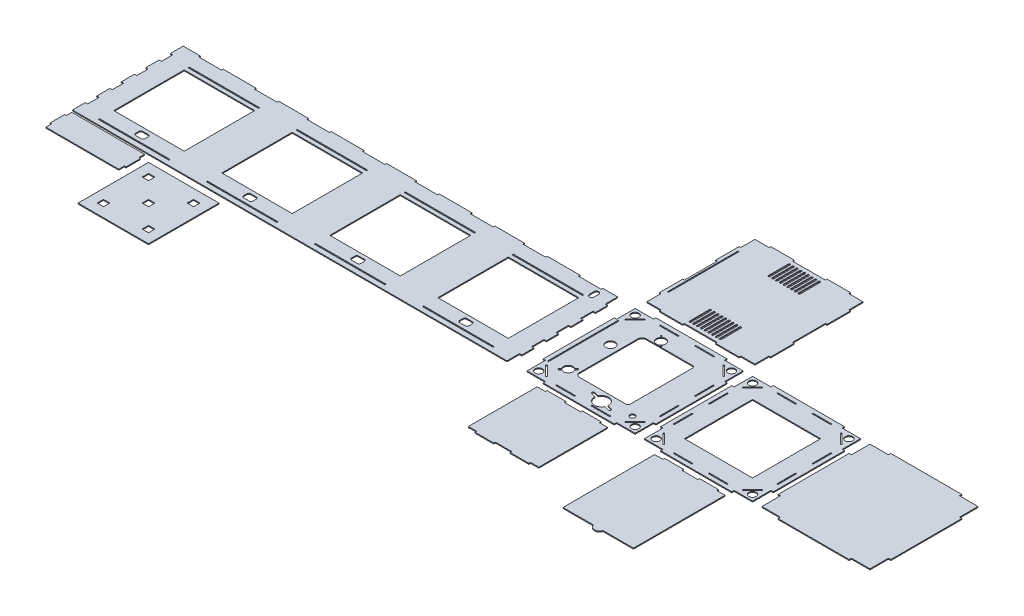
SolidWorks part; units mm, degrees
ref_plane "Front" through (0, 0, 0) normal (0, 0, 1) x (1, 0, 0)
ref_plane "Top" through (0, 0, 0) normal (0, 1, 0) x (1, 0, 0)
ref_plane "Right" through (0, 0, 0) normal (1, 0, 0) x (0, 0, -1)
sketch "Sketch1" plane through (0, 0, 0) normal (0, 1, 0) x (1, 0, 0)
  line L0 (0, 0) -> (438.15, 0) construction
  line L2 (-146.05, 149.606) -> (-146.05, -149.606) construction
  line L4 (146.05, 149.606) -> (146.05, -149.606) construction
  line L5 (-146.05, 149.606) -> (146.05, -149.606) construction
  line L6 (-146.05, -149.606) -> (146.05, 149.606) construction
  line L11 (146.05, 149.606) -> (438.15, 149.606)
  line L12 (146.05, 149.606) -> (146.05, -149.606) construction
  line L13 (146.05, -149.606) -> (438.15, -149.606)
  line L14 (438.15, 149.606) -> (438.15, -149.606) construction
  line L19 (-146.05, -149.606) -> (-438.15, -149.606)
  line L20 (-146.05, -149.606) -> (-146.05, 149.606) construction
  line L21 (-146.05, 149.606) -> (-438.15, 149.606)
  line L28 (146.05, -149.606) -> (-146.05, -149.606)
  line L34 (146.05, 149.606) -> (-146.05, 149.606)
  line L35 (-438.15, 149.606) -> (-438.15, -149.606) construction
  line L43 (-438.15, 149.606) -> (-730.25, 149.606)
  line L44 (-730.25, 149.606) -> (-730.25, -149.606) construction
  line L45 (-730.25, -149.606) -> (-438.15, -149.606)
  line L46 (438.15, 149.606) -> (438.15, 116.078)
  line L47 (438.15, 116.078) -> (444.5, 116.078)
  line L48 (444.5, 116.078) -> (444.5, 83.185)
  line L49 (444.5, 83.185) -> (438.15, 83.185)
  line L50 (438.15, 83.185) -> (438.15, 49.657)
  line L51 (438.15, 49.657) -> (444.5, 49.657)
  line L63 (444.5, 49.657) -> (444.5, 16.764)
  line L64 (444.5, 16.764) -> (438.15, 16.764)
  line L65 (438.15, 16.764) -> (438.15, -16.764)
  line L66 (438.15, -16.764) -> (444.5, -16.764)
  line L67 (444.5, -16.764) -> (444.5, -49.657)
  line L68 (444.5, -49.657) -> (438.15, -49.657)
  line L69 (438.15, -49.657) -> (438.15, -83.185)
  line L70 (438.15, -83.185) -> (444.5, -83.185)
  line L71 (444.5, -83.185) -> (444.5, -116.078)
  line L72 (444.5, -116.078) -> (438.15, -116.078)
  line L73 (438.15, -116.078) -> (438.15, -149.606)
  line L74 (-730.25, 149.606) -> (-736.6, 149.606)
  line L76 (-736.6, 114.8715) -> (-730.25, 114.8715)
  line L78 (-730.25, 84.3915) -> (-736.6, 84.3915)
  line L80 (-736.6, 48.4505) -> (-730.25, 48.4505)
  line L82 (-730.25, 17.9705) -> (-736.6, 17.9705)
  line L84 (-736.6, -17.9705) -> (-730.25, -17.9705)
  line L86 (-730.25, -48.4505) -> (-736.6, -48.4505)
  line L88 (-736.6, -84.3915) -> (-730.25, -84.3915)
  line L90 (-730.25, -114.8715) -> (-736.6, -114.8715)
  line L92 (-736.6, -149.606) -> (-730.25, -149.606)
  line L93 (444.5, 33.2105) -> (-730.25, 33.2105) construction
  line L94 (-730.25, 99.6315) -> (444.5, 99.6315) construction
  line L95 (-736.6, 149.606) -> (-736.6, 114.8715)
  line L96 (-736.6, 84.3915) -> (-736.6, 48.4505)
  line L97 (-730.25, 114.8715) -> (-730.25, 84.3915)
  line L98 (-730.25, 48.4505) -> (-730.25, 17.9705)
  line L99 (-730.25, -17.9705) -> (-730.25, -48.4505)
  line L100 (-730.25, -84.3915) -> (-730.25, -114.8715)
  line L101 (-730.25, -99.6315) -> (444.5, -99.6315) construction
  line L102 (-730.25, -33.2105) -> (444.5, -33.2105) construction
  line L103 (-736.6, 17.9705) -> (-736.6, -17.9705)
  line L104 (-736.6, -48.4505) -> (-736.6, -84.3915)
  line L105 (-736.6, -114.8715) -> (-736.6, -149.606)
  point P0 (0, 0)
  dimension "D1" = 292.1
  dimension "D2" = 299.212
  dimension "D3" = 6.35
  dimension "D4" = 32.893
  dimension "D5" = 30.48
extrude "Boss-Extrude1" add sketch "Sketch1" along normal blind 2.54
sketch "Sketch4" plane through (0, 2.54, 0) normal (0, 1, 0) x (1, 0, 0)
  line L0 (-438.15, 149.606) -> (-438.15, -149.606) construction
  line L1 (-438.15, 149.606) -> (-438.15, -149.606)
  line L2 (-146.05, 149.606) -> (-146.05, -149.606) construction
  line L3 (-146.05, 149.606) -> (-146.05, -149.606)
  line L4 (146.05, 149.606) -> (146.05, -149.606) construction
  line L5 (146.05, 149.606) -> (146.05, -149.606)
sketch "Sketch5" plane through (0, 2.54, 0) normal (0, 1, 0) x (1, 0, 0)
  line L0 (-730.25, -17.9705) -> (-730.25, 17.9705) construction
  line L1 (-438.15, 0) -> (-730.25, 0) construction
  line L2 (-438.15, 149.606) -> (-438.15, -149.606) construction
  line L3 (-438.15, 0) -> (-146.05, 0) construction
  line L4 (-146.05, 149.606) -> (-146.05, -149.606) construction
  line L5 (-146.05, 0) -> (146.05, 0) construction
  line L6 (146.05, 149.606) -> (146.05, -149.606) construction
  line L7 (146.05, 0) -> (438.15, 0) construction
  line L8 (438.15, -16.764) -> (438.15, 16.764) construction
  line L9 (-584.2, 0) -> (-584.2, -149.606) construction
  line L10 (-736.6, -149.606) -> (438.15, -149.606) construction
  line L11 (-292.1, 0) -> (-292.1, -149.606) construction
  line L12 (0, 0) -> (0, -149.606) construction
  line L13 (292.1, 0) -> (292.1, -149.606) construction
  line L14 (-488.95, -136.906) -> (-488.95, -149.606) construction
  line L15 (-679.45, -133.604) -> (-488.95, -133.604)
  line L16 (-679.45, -133.604) -> (-679.45, -136.906)
  line L17 (-679.45, -136.906) -> (-488.95, -136.906)
  line L18 (-488.95, -133.604) -> (-488.95, -136.906)
  line L19 (-679.45, -133.604) -> (-488.95, -136.906) construction
  line L20 (-679.45, -136.906) -> (-488.95, -133.604) construction
  line L21 (-387.35, -133.604) -> (-196.85, -133.604)
  line L22 (-387.35, -133.604) -> (-387.35, -136.906)
  line L23 (-387.35, -136.906) -> (-196.85, -136.906)
  line L24 (-196.85, -133.604) -> (-196.85, -136.906)
  line L25 (-387.35, -133.604) -> (-196.85, -136.906) construction
  line L26 (-387.35, -136.906) -> (-196.85, -133.604) construction
  line L27 (-95.25, -136.906) -> (95.25, -136.906)
  line L28 (-95.25, -136.906) -> (-95.25, -133.604)
  line L29 (-95.25, -133.604) -> (95.25, -133.604)
  line L30 (95.25, -136.906) -> (95.25, -133.604)
  line L31 (-95.25, -136.906) -> (95.25, -133.604) construction
  line L32 (-95.25, -133.604) -> (95.25, -136.906) construction
  line L33 (196.85, -136.906) -> (387.35, -136.906)
  line L34 (196.85, -136.906) -> (196.85, -133.604)
  line L35 (196.85, -133.604) -> (387.35, -133.604)
  line L36 (387.35, -136.906) -> (387.35, -133.604)
  line L37 (196.85, -136.906) -> (387.35, -133.604) construction
  line L38 (196.85, -133.604) -> (387.35, -136.906) construction
  line L39 (196.85, 133.604) -> (387.35, 136.906) construction
  line L40 (196.85, 136.906) -> (387.35, 133.604) construction
  line L41 (-95.25, 133.604) -> (95.25, 136.906) construction
  line L42 (-95.25, 136.906) -> (95.25, 133.604) construction
  line L43 (-387.35, 136.906) -> (-196.85, 133.604) construction
  line L44 (-387.35, 133.604) -> (-196.85, 136.906) construction
  line L45 (-679.45, 136.906) -> (-488.95, 133.604) construction
  line L46 (-679.45, 133.604) -> (-488.95, 136.906) construction
  line L47 (-584.2, 0) -> (-584.2, 107.061) construction
  line L48 (387.35, 136.906) -> (387.35, 133.604) construction
  line L49 (196.85, 133.604) -> (387.35, 133.604) construction
  line L50 (196.85, 136.906) -> (196.85, 133.604) construction
  line L51 (196.85, 136.906) -> (387.35, 136.906) construction
  line L52 (95.25, 136.906) -> (95.25, 133.604) construction
  line L53 (-95.25, 133.604) -> (95.25, 133.604) construction
  line L54 (-95.25, 136.906) -> (-95.25, 133.604) construction
  line L55 (-95.25, 136.906) -> (95.25, 136.906) construction
  line L56 (-196.85, 133.604) -> (-196.85, 136.906) construction
  line L57 (-387.35, 136.906) -> (-196.85, 136.906) construction
  line L58 (-387.35, 133.604) -> (-387.35, 136.906) construction
  line L59 (-387.35, 133.604) -> (-196.85, 133.604) construction
  line L60 (-488.95, 133.604) -> (-488.95, 136.906) construction
  line L61 (-679.45, 136.906) -> (-488.95, 136.906) construction
  line L62 (-679.45, 133.604) -> (-679.45, 136.906) construction
  line L63 (-679.45, 133.604) -> (-488.95, 133.604) construction
  line L64 (-292.1, 0) -> (-292.1, 107.061) construction
  line L65 (-679.45, 95.25) -> (-488.95, 95.25)
  line L66 (-679.45, 95.25) -> (-679.45, -95.25)
  line L67 (-679.45, -95.25) -> (-488.95, -95.25)
  line L68 (-488.95, 95.25) -> (-488.95, -95.25)
  line L69 (-679.45, 95.25) -> (-488.95, -95.25) construction
  line L70 (-679.45, -95.25) -> (-488.95, 95.25) construction
  line L71 (-387.35, 95.25) -> (-196.85, 95.25)
  line L72 (-387.35, 95.25) -> (-387.35, -95.25)
  line L73 (-387.35, -95.25) -> (-196.85, -95.25)
  line L74 (-196.85, 95.25) -> (-196.85, -95.25)
  line L75 (-387.35, 95.25) -> (-196.85, -95.25) construction
  line L76 (-387.35, -95.25) -> (-196.85, 95.25) construction
  line L77 (-95.25, 95.25) -> (95.25, 95.25)
  line L78 (-95.25, 95.25) -> (-95.25, -95.25)
  line L79 (-95.25, -95.25) -> (95.25, -95.25)
  line L80 (95.25, 95.25) -> (95.25, -95.25)
  line L81 (-95.25, 95.25) -> (95.25, -95.25) construction
  line L82 (-95.25, -95.25) -> (95.25, 95.25) construction
  line L83 (196.85, 95.25) -> (387.35, 95.25)
  line L84 (196.85, 95.25) -> (196.85, -95.25)
  line L85 (196.85, -95.25) -> (387.35, -95.25)
  line L86 (387.35, 95.25) -> (387.35, -95.25)
  line L87 (196.85, 95.25) -> (387.35, -95.25) construction
  line L88 (196.85, -95.25) -> (387.35, 95.25) construction
  line L89 (0, 0) -> (0, 107.061) construction
  line L90 (292.1, 0) -> (292.1, 107.061) construction
  line L91 (-387.35, -95.25) -> (-387.35, -133.604) construction
  line L92 (-679.45, 108.712) -> (-488.95, 108.712)
  line L93 (-679.45, 108.712) -> (-679.45, 105.41)
  line L94 (-679.45, 105.41) -> (-488.95, 105.41)
  line L95 (-488.95, 108.712) -> (-488.95, 105.41)
  line L96 (-679.45, 108.712) -> (-488.95, 105.41) construction
  line L97 (-679.45, 105.41) -> (-488.95, 108.712) construction
  line L98 (-387.35, 108.712) -> (-196.85, 108.712)
  line L99 (-387.35, 108.712) -> (-387.35, 105.41)
  line L100 (-387.35, 105.41) -> (-196.85, 105.41)
  line L101 (-196.85, 108.712) -> (-196.85, 105.41)
  line L102 (-387.35, 108.712) -> (-196.85, 105.41) construction
  line L103 (-387.35, 105.41) -> (-196.85, 108.712) construction
  line L104 (-95.25, 108.712) -> (95.25, 108.712)
  line L105 (-95.25, 108.712) -> (-95.25, 105.41)
  line L106 (-95.25, 105.41) -> (95.25, 105.41)
  line L107 (95.25, 108.712) -> (95.25, 105.41)
  line L108 (-95.25, 108.712) -> (95.25, 105.41) construction
  line L109 (-95.25, 105.41) -> (95.25, 108.712) construction
  line L110 (196.85, 108.712) -> (387.35, 108.712)
  line L111 (196.85, 108.712) -> (196.85, 105.41)
  line L112 (196.85, 105.41) -> (387.35, 105.41)
  line L113 (387.35, 108.712) -> (387.35, 105.41)
  line L114 (196.85, 108.712) -> (387.35, 105.41) construction
  line L115 (196.85, 105.41) -> (387.35, 108.712) construction
  line L116 (-196.85, -95.25) -> (-196.85, -133.604) construction
  line L117 (-196.85, -114.427) -> (-387.35, -114.427) construction
  line L118 (-7.62, -124.079) -> (7.62, -124.079)
  line L119 (-299.72, -104.775) -> (-284.48, -104.775)
  line L120 (-304.8, -109.855) -> (-304.8, -118.999)
  line L121 (-299.72, -124.079) -> (-284.48, -124.079)
  line L122 (-279.4, -109.855) -> (-279.4, -118.999)
  line L123 (-304.8, -104.775) -> (-279.4, -124.079) construction
  line L124 (-304.8, -124.079) -> (-279.4, -104.775) construction
  line L125 (-12.7, -109.855) -> (-12.7, -118.999)
  line L126 (-7.62, -104.775) -> (7.62, -104.775)
  line L127 (12.7, -109.855) -> (12.7, -118.999)
  line L128 (284.48, -124.079) -> (299.72, -124.079)
  line L129 (279.4, -109.855) -> (279.4, -118.999)
  line L130 (284.48, -104.775) -> (299.72, -104.775)
  line L131 (304.8, -109.855) -> (304.8, -118.999)
  line L132 (-596.9, -109.855) -> (-596.9, -118.999)
  line L133 (-591.82, -104.775) -> (-576.58, -104.775)
  line L134 (-571.5, -109.855) -> (-571.5, -118.999)
  line L135 (-591.82, -124.079) -> (-576.58, -124.079)
  line L136 (438.15, 149.606) -> (-736.6, 149.606) construction
  line L137 (400.05, 130.302) -> (400.05, 117.602) construction
  line L138 (406.4, 130.302) -> (406.4, 117.602)
  line L139 (393.7, 130.302) -> (393.7, 117.602)
  line L140 (438.15, 116.078) -> (438.15, 149.606) construction
  arc A0 (-284.48, -104.775) -> (-279.4, -109.855) centre (-284.48, -109.855) cw
  arc A1 (-279.4, -118.999) -> (-284.48, -124.079) centre (-284.48, -118.999) cw
  arc A2 (-299.72, -124.079) -> (-304.8, -118.999) centre (-299.72, -118.999) cw
  arc A3 (-304.8, -109.855) -> (-299.72, -104.775) centre (-299.72, -109.855) cw
  arc A4 (-7.62, -124.079) -> (-12.7, -118.999) centre (-7.62, -118.999) cw
  arc A5 (-12.7, -109.855) -> (-7.62, -104.775) centre (-7.62, -109.855) cw
  arc A6 (7.62, -104.775) -> (12.7, -109.855) centre (7.62, -109.855) cw
  arc A7 (12.7, -118.999) -> (7.62, -124.079) centre (7.62, -118.999) cw
  arc A8 (284.48, -124.079) -> (279.4, -118.999) centre (284.48, -118.999) cw
  arc A9 (279.4, -109.855) -> (284.48, -104.775) centre (284.48, -109.855) cw
  arc A10 (299.72, -104.775) -> (304.8, -109.855) centre (299.72, -109.855) cw
  arc A11 (304.8, -118.999) -> (299.72, -124.079) centre (299.72, -118.999) cw
  arc A12 (-596.9, -109.855) -> (-591.82, -104.775) centre (-591.82, -109.855) cw
  arc A13 (-591.82, -124.079) -> (-596.9, -118.999) centre (-591.82, -118.999) cw
  arc A14 (-576.58, -104.775) -> (-571.5, -109.855) centre (-576.58, -109.855) cw
  arc A15 (-571.5, -118.999) -> (-576.58, -124.079) centre (-576.58, -118.999) cw
  arc A16 (406.4, 130.302) -> (393.7, 130.302) centre (400.05, 130.302) ccw
  arc A17 (393.7, 117.602) -> (406.4, 117.602) centre (400.05, 117.602) ccw
  point P27 (-584.2, -135.255)
  point P32 (-292.1, -135.255)
  point P37 (0, -135.255)
  point P42 (292.1, -135.255)
  point P66 (292.1, 135.255)
  point P67 (0, 135.255)
  point P68 (-292.1, 135.255)
  point P69 (-584.2, 135.255)
  point P106 (-292.1, -114.427)
  point P148 (0, -124.079)
  point P161 (-584.2, -124.079)
  point P165 (400.05, 123.952)
  point P172 (400.05, 135.255)
  point P173 (400.05, 118.0137)
  dimension "D5" = 10.16
  dimension "D7" = 9.525
  dimension "D9" = 5.08
  dimension "D14" = 25.4
  dimension "D16" = 2.54
  dimension "D1" = 12.7
  dimension "D2" = 3.302
  dimension "D3" = 190.5
  dimension "D4" = 190.5
  dimension "D6" = 9.525
  dimension "D8" = 25.4
  dimension "D10" = 3
  dimension "D12" = 40.894
  dimension "D13" = 12.7
  dimension "D15" = 38.1
  dimension "D11" = 2
extrude "Cut-Extrude2" cut sketch "Sketch5" against normal through all
sketch "Sketch6" plane through (0, 0, 0) normal (0, 1, 0) x (1, 0, 0)
  line L0 (0, 0) -> (635, 0) construction
  line L1 (635, 0) -> (635, 149.225) construction
  line L2 (488.95, 146.05) -> (781.05, 146.05) construction
  line L3 (488.95, 146.05) -> (488.95, -146.05) construction
  line L4 (488.95, -146.05) -> (781.05, -146.05) construction
  line L5 (781.05, 146.05) -> (781.05, -146.05) construction
  line L6 (488.95, 146.05) -> (781.05, -146.05) construction
  line L7 (488.95, -146.05) -> (781.05, 146.05) construction
  line L8 (635, 0) -> (784.225, 0) construction
  line L9 (635, 0) -> (635, -149.225) construction
  line L10 (488.95, 96.139) -> (488.95, 146.05)
  line L11 (538.861, 152.4) -> (731.139, 152.4)
  line L12 (538.861, 152.4) -> (538.861, 146.05)
  line L13 (538.861, 146.05) -> (731.139, 146.05) construction
  line L14 (731.139, 152.4) -> (731.139, 146.05)
  line L15 (538.861, 152.4) -> (731.139, 146.05) construction
  line L16 (538.861, 146.05) -> (731.139, 152.4) construction
  line L17 (787.4, -96.139) -> (781.05, -96.139)
  line L18 (787.4, -96.139) -> (787.4, 96.139)
  line L19 (787.4, 96.139) -> (781.05, 96.139)
  line L20 (781.05, -96.139) -> (781.05, 96.139) construction
  line L21 (787.4, -96.139) -> (781.05, 96.139) construction
  line L22 (787.4, 96.139) -> (781.05, -96.139) construction
  line L23 (538.861, -152.4) -> (731.139, -152.4)
  line L24 (538.861, -152.4) -> (538.861, -146.05)
  line L25 (538.861, -146.05) -> (731.139, -146.05) construction
  line L26 (731.139, -152.4) -> (731.139, -146.05)
  line L27 (538.861, -152.4) -> (731.139, -146.05) construction
  line L28 (538.861, -146.05) -> (731.139, -152.4) construction
  line L29 (482.6, 96.139) -> (488.95, 96.139)
  line L30 (482.6, 96.139) -> (482.6, -96.139)
  line L31 (482.6, -96.139) -> (488.95, -96.139)
  line L32 (488.95, 96.139) -> (488.95, -96.139) construction
  line L33 (482.6, 96.139) -> (488.95, -96.139) construction
  line L34 (482.6, -96.139) -> (488.95, 96.139) construction
  line L35 (488.95, 146.05) -> (538.861, 146.05)
  line L36 (731.139, 146.05) -> (781.05, 146.05)
  line L37 (781.05, 146.05) -> (781.05, 96.139)
  line L38 (781.05, -96.139) -> (781.05, -146.05)
  line L39 (781.05, -146.05) -> (731.139, -146.05)
  line L40 (538.861, -146.05) -> (488.95, -146.05)
  line L41 (488.95, -146.05) -> (488.95, -96.139)
  line L42 (800.1, 96.139) -> (800.1, -96.139)
  line L43 (800.1, 96.139) -> (806.45, 96.139)
  line L44 (806.45, 96.139) -> (806.45, 146.05)
  line L45 (806.45, 146.05) -> (856.361, 146.05)
  line L46 (856.361, 152.4) -> (856.361, 146.05)
  line L47 (856.361, 152.4) -> (1048.639, 152.4)
  line L48 (1048.639, 152.4) -> (1048.639, 146.05)
  line L49 (1048.639, 146.05) -> (1098.55, 146.05)
  line L50 (1098.55, 146.05) -> (1098.55, 96.139)
  line L51 (1104.9, 96.139) -> (1098.55, 96.139)
  line L52 (1104.9, -96.139) -> (1104.9, 96.139)
  line L53 (1104.9, -96.139) -> (1098.55, -96.139)
  line L54 (1098.55, -96.139) -> (1098.55, -146.05)
  line L55 (1098.55, -146.05) -> (1048.639, -146.05)
  line L56 (1048.639, -152.4) -> (1048.639, -146.05)
  line L57 (856.361, -152.4) -> (1048.639, -152.4)
  line L58 (856.361, -152.4) -> (856.361, -146.05)
  line L59 (856.361, -146.05) -> (806.45, -146.05)
  line L60 (806.45, -146.05) -> (806.45, -96.139)
  line L61 (800.1, -96.139) -> (806.45, -96.139)
  line L62 (806.45, 146.05) -> (1098.55, -146.05) construction
  line L63 (1117.6, 96.139) -> (1117.6, -96.139)
  line L64 (1117.6, 96.139) -> (1123.95, 96.139)
  line L65 (1123.95, 96.139) -> (1123.95, 146.05)
  line L66 (1123.95, 146.05) -> (1173.861, 146.05)
  line L67 (1173.861, 152.4) -> (1173.861, 146.05)
  line L68 (1173.861, 152.4) -> (1366.139, 152.4)
  line L69 (1366.139, 152.4) -> (1366.139, 146.05)
  line L70 (1366.139, 146.05) -> (1416.05, 146.05)
  line L71 (1416.05, 146.05) -> (1416.05, 96.139)
  line L72 (1422.4, 96.139) -> (1416.05, 96.139)
  line L73 (1422.4, -96.139) -> (1422.4, 96.139)
  line L74 (1422.4, -96.139) -> (1416.05, -96.139)
  line L75 (1416.05, -96.139) -> (1416.05, -146.05)
  line L76 (1416.05, -146.05) -> (1366.139, -146.05)
  line L77 (1366.139, -152.4) -> (1366.139, -146.05)
  line L78 (1173.861, -152.4) -> (1366.139, -152.4)
  line L79 (1173.861, -152.4) -> (1173.861, -146.05)
  line L80 (1173.861, -146.05) -> (1123.95, -146.05)
  line L81 (1123.95, -146.05) -> (1123.95, -96.139)
  line L82 (1117.6, -96.139) -> (1123.95, -96.139)
  line L84 (860.425, 92.075) -> (1044.575, 92.075)
  line L85 (860.425, 92.075) -> (860.425, -92.075)
  line L86 (860.425, -92.075) -> (1044.575, -92.075)
  line L87 (1044.575, 92.075) -> (1044.575, -92.075)
  line L88 (860.425, 92.075) -> (1044.575, -92.075) construction
  line L89 (860.425, -92.075) -> (1044.575, 92.075) construction
  point P22 (485.775, 0)
  point P67 (952.5, 0)
  dimension "D1" = 292.1
  dimension "D2" = 292.1
  dimension "D3" = 6.35
  dimension "D4" = 192.278
  dimension "D5" = 635
  dimension "D7" = 12.7
  dimension "D8" = 184.15
  dimension "D6" = 3
extrude "Boss-Extrude2" add sketch "Sketch6" along normal blind 2.54 separate body
sketch "Sketch7" plane through (0, 0, 0) normal (0, 1, 0) x (1, 0, 0)
  line L0 (-679.45, 105.41) -> (-679.45, -91.186) construction
  line L1 (-732.155, -155.956) -> (-535.559, -155.956)
  line L2 (-732.155, -155.956) -> (-732.155, -171.196)
  line L3 (-732.155, -225.806) -> (-535.559, -225.806)
  line L4 (-535.559, -155.956) -> (-535.559, -171.196)
  line L5 (-732.155, -155.956) -> (-535.559, -225.806) construction
  line L6 (-732.155, -225.806) -> (-535.559, -155.956) construction
  line L7 (-679.45, 95.25) -> (-679.45, -95.25) construction
  line L8 (-679.45, -91.186) -> (-679.45, -95.25) construction
  line L9 (488.95, -96.139) -> (488.95, -146.05) construction
  line L10 (488.95, -146.05) -> (538.861, -146.05) construction
  line L12 (-732.155, -171.196) -> (-736.6, -171.196)
  line L13 (502.77, -105.2892) -> (529.7108, -132.23) construction
  line L14 (502.77, -105.2892) -> (500.4351, -107.6241) construction
  line L15 (500.4351, -107.6241) -> (527.3759, -134.5649) construction
  line L16 (529.7108, -132.23) -> (527.3759, -134.5649) construction
  line L17 (502.77, -105.2892) -> (527.3759, -134.5649) construction
  line L18 (500.4351, -107.6241) -> (529.7108, -132.23) construction
  line L19 (-736.6, -171.196) -> (-736.6, -210.566)
  line L20 (-736.6, -210.566) -> (-732.155, -210.566)
  line L21 (488.95, -96.139) -> (538.861, -146.05) construction
  line L22 (515.0729, -119.9271) -> (513.9055, -121.0945) construction
  line L23 (-732.155, -210.566) -> (-732.155, -225.806)
  line L24 (-535.559, -171.196) -> (-531.114, -171.196)
  line L25 (-531.114, -171.196) -> (-531.114, -210.566)
  line L26 (-531.114, -210.566) -> (-535.559, -210.566)
  line L27 (-535.559, -210.566) -> (-535.559, -225.806)
  line L28 (-736.6, -149.606) -> (438.15, -149.606) construction
  line L29 (-736.6, -114.8715) -> (-736.6, -149.606) construction
  point P0 (-633.857, -190.881)
  point P14 (515.0729, -119.9271)
  dimension "D1" = 69.85
  dimension "D2" = 4.064
  dimension "D3" = 3.302
  dimension "D4" = 39.37
  dimension "D5" = 38.1
  dimension "D6" = 4.445
  dimension "D7" = 6.35
extrude "Boss-Extrude3" add sketch "Sketch7" along normal blind 2.54 separate body
sketch "Sketch8" plane through (0, 2.54, 0) normal (0, 1, 0) x (1, 0, 0)
  line L0 (500.4351, -107.6241) -> (527.3759, -134.5649) construction
  line L1 (529.7108, -132.23) -> (527.3759, -134.5649) construction
  line L2 (502.77, -105.2892) -> (529.7108, -132.23) construction
  line L3 (502.77, -105.2892) -> (500.4351, -107.6241) construction
  line L4 (500.4351, -107.6241) -> (527.3759, -134.5649)
  line L5 (529.7108, -132.23) -> (527.3759, -134.5649)
  line L6 (502.77, -105.2892) -> (529.7108, -132.23)
  line L7 (502.77, -105.2892) -> (500.4351, -107.6241)
  line L8 (488.95, 146.05) -> (781.05, -146.05) construction
  line L9 (529.7108, 132.23) -> (502.77, 105.2892)
  line L10 (529.7108, 132.23) -> (527.3759, 134.5649)
  line L11 (527.3759, 134.5649) -> (500.4351, 107.6241)
  line L12 (502.77, 105.2892) -> (500.4351, 107.6241)
  line L13 (767.23, 105.2892) -> (740.2892, 132.23)
  line L14 (767.23, 105.2892) -> (769.5649, 107.6241)
  line L15 (769.5649, 107.6241) -> (742.6241, 134.5649)
  line L16 (740.2892, 132.23) -> (742.6241, 134.5649)
  line L17 (740.2892, -132.23) -> (767.23, -105.2892)
  line L18 (740.2892, -132.23) -> (742.6241, -134.5649)
  line L19 (742.6241, -134.5649) -> (769.5649, -107.6241)
  line L20 (767.23, -105.2892) -> (769.5649, -107.6241)
  line L21 (806.45, -96.139) -> (856.361, -146.05) construction
  line L22 (817.9351, -107.6241) -> (820.27, -105.2892)
  line L23 (820.27, -105.2892) -> (847.2108, -132.23)
  line L24 (847.2108, -132.23) -> (844.8759, -134.5649)
  line L25 (831.4055, -121.0945) -> (833.7404, -118.7596) construction
  line L26 (817.9351, -107.6241) -> (844.8759, -134.5649)
  line L27 (806.45, 146.05) -> (1098.55, -146.05) construction
  line L28 (820.27, 105.2892) -> (817.9351, 107.6241)
  line L29 (844.8759, 134.5649) -> (817.9351, 107.6241)
  line L30 (844.8759, 134.5649) -> (847.2108, 132.23)
  line L31 (847.2108, 132.23) -> (820.27, 105.2892)
  line L32 (1057.7892, 132.23) -> (1060.1241, 134.5649)
  line L33 (1087.0649, 107.6241) -> (1060.1241, 134.5649)
  line L34 (1087.0649, 107.6241) -> (1084.73, 105.2892)
  line L35 (1084.73, 105.2892) -> (1057.7892, 132.23)
  line L36 (1084.73, -105.2892) -> (1087.0649, -107.6241)
  line L37 (1060.1241, -134.5649) -> (1087.0649, -107.6241)
  line L38 (1060.1241, -134.5649) -> (1057.7892, -132.23)
  line L39 (1057.7892, -132.23) -> (1084.73, -105.2892)
  circle A0 centre (635, 0) radius 20.7898 construction
  circle A1 centre (635, 0) radius 20.7898 construction
  circle A2 centre (635, 0) radius 20.7898 construction
  circle A3 centre (635, 0) radius 20.7898 construction
  circle A4 centre (952.5, 0) radius 130.2137 construction
  circle A5 centre (822.1654, 130.3346) radius 10
  circle A9 centre (1082.8346, 130.3346) radius 10
  circle A10 centre (1082.8346, -130.3346) radius 10
  circle A11 centre (822.1654, -130.3346) radius 10
  circle A12 centre (504.6654, 130.3346) radius 10
  circle A13 centre (765.3346, 130.3346) radius 10
  circle A14 centre (765.3346, -130.3346) radius 10
  circle A15 centre (504.6654, -130.3346) radius 10
  point P28 (635, 0)
  point P58 (952.5, 0)
  point P67 (952.5, 0)
  point P76 (635, 0)
  dimension "D3" = 20
  dimension "D4" = 22.225
  dimension "D6" = 22.225
  dimension "D1" = 4
  dimension "D2" = 4
  dimension "D5" = 4
  dimension "D7" = 4
extrude "Cut-Extrude3" cut sketch "Sketch8" against normal through all
sketch "Sketch9" plane through (0, 0, 0) normal (0, 1, 0) x (1, 0, 0)
  line L0 (-736.6, -149.606) -> (438.15, -149.606) construction
  line L1 (-511.114, -169.606) -> (-320.614, -169.606)
  line L2 (-511.114, -169.606) -> (-511.114, -360.106)
  line L3 (-511.114, -360.106) -> (-320.614, -360.106)
  line L4 (-320.614, -169.606) -> (-320.614, -360.106)
  line L5 (-511.114, -169.606) -> (-320.614, -360.106) construction
  line L6 (-511.114, -360.106) -> (-320.614, -169.606) construction
  line L7 (-424.5, -256.22) -> (-407.228, -256.22)
  line L8 (-424.5, -256.22) -> (-424.5, -273.492)
  line L9 (-424.5, -273.492) -> (-407.228, -273.492)
  line L10 (-407.228, -256.22) -> (-407.228, -273.492)
  line L11 (-424.5, -256.22) -> (-407.228, -273.492) construction
  line L12 (-424.5, -273.492) -> (-407.228, -256.22) construction
  line L13 (-476.7627, -203.9573) -> (-354.9653, -203.9573) construction
  line L14 (-476.7627, -203.9573) -> (-476.7627, -325.7547) construction
  line L15 (-476.7627, -325.7547) -> (-354.9653, -325.7547) construction
  line L16 (-354.9653, -203.9573) -> (-354.9653, -325.7547) construction
  line L17 (-476.7627, -203.9573) -> (-354.9653, -325.7547) construction
  line L18 (-476.7627, -325.7547) -> (-354.9653, -203.9573) construction
  line L19 (-485.3987, -195.3213) -> (-468.1267, -195.3213)
  line L20 (-485.3987, -195.3213) -> (-485.3987, -212.5933)
  line L21 (-485.3987, -212.5933) -> (-468.1267, -212.5933)
  line L22 (-468.1267, -195.3213) -> (-468.1267, -212.5933)
  line L23 (-485.3987, -195.3213) -> (-468.1267, -212.5933) construction
  line L24 (-485.3987, -212.5933) -> (-468.1267, -195.3213) construction
  line L25 (-485.3987, -317.1187) -> (-468.1267, -317.1187)
  line L26 (-485.3987, -317.1187) -> (-485.3987, -334.3907)
  line L27 (-485.3987, -334.3907) -> (-468.1267, -334.3907)
  line L28 (-468.1267, -317.1187) -> (-468.1267, -334.3907)
  line L29 (-485.3987, -317.1187) -> (-468.1267, -334.3907) construction
  line L30 (-485.3987, -334.3907) -> (-468.1267, -317.1187) construction
  line L31 (-346.3293, -317.1187) -> (-363.6013, -317.1187)
  line L32 (-346.3293, -317.1187) -> (-346.3293, -334.3907)
  line L33 (-346.3293, -334.3907) -> (-363.6013, -334.3907)
  line L34 (-363.6013, -317.1187) -> (-363.6013, -334.3907)
  line L35 (-346.3293, -317.1187) -> (-363.6013, -334.3907) construction
  line L36 (-346.3293, -334.3907) -> (-363.6013, -317.1187) construction
  line L37 (-363.6013, -195.3213) -> (-346.3293, -195.3213)
  line L38 (-363.6013, -195.3213) -> (-363.6013, -212.5933)
  line L39 (-363.6013, -212.5933) -> (-346.3293, -212.5933)
  line L40 (-346.3293, -195.3213) -> (-346.3293, -212.5933)
  line L41 (-363.6013, -195.3213) -> (-346.3293, -212.5933) construction
  line L42 (-363.6013, -212.5933) -> (-346.3293, -195.3213) construction
  line L43 (-531.114, -210.566) -> (-531.114, -171.196) construction
  point P0 (-415.864, -264.856)
  point P5 (-415.864, -264.856)
  point P12 (-415.864, -264.856)
  dimension "D1" = 190.5
  dimension "D2" = 190.5
  dimension "D3" = 17.272
  dimension "D4" = 17.272
  dimension "D5" = 20
  dimension "D6" = 20
  dimension "D7" = 121.7975
extrude "Boss-Extrude4" add sketch "Sketch9" along normal blind 2.54 separate body
sketch "Sketch10" plane through (0, 2.54, 0) normal (0, 1, 0) x (1, 0, 0)
  line L0 (-488.95, 95.25) -> (-679.45, 95.25) construction
  line L1 (-196.85, 95.25) -> (-387.35, 95.25) construction
  line L2 (95.25, 95.25) -> (-95.25, 95.25) construction
  line L3 (387.35, 95.25) -> (196.85, 95.25) construction
  line L4 (-574.04, 95.25) -> (-594.36, 95.25)
  line L5 (-281.94, 95.25) -> (-302.26, 95.25)
  line L6 (10.16, 95.25) -> (-10.16, 95.25)
  line L7 (302.26, 95.25) -> (281.94, 95.25)
  line L8 (-679.45, -90.805) -> (-488.95, -90.805)
  line L9 (-584.2, -90.805) -> (-584.2, -95.25) construction
  line L14 (-679.45, 95.25) -> (-679.45, -95.25) construction
  line L15 (-488.95, -95.25) -> (-488.95, 95.25) construction
  line L16 (-679.45, -95.25) -> (-488.95, -95.25) construction
  line L17 (-387.35, -90.805) -> (-196.85, -90.805)
  line L18 (-387.35, 95.25) -> (-387.35, -95.25) construction
  line L19 (-196.85, -95.25) -> (-196.85, 95.25) construction
  line L20 (-95.25, -90.805) -> (95.25, -90.805)
  line L21 (-95.25, 95.25) -> (-95.25, -95.25) construction
  line L22 (95.25, -95.25) -> (95.25, 95.25) construction
  line L23 (196.85, -90.805) -> (387.35, -90.805)
  line L24 (196.85, 95.25) -> (196.85, -95.25) construction
  line L25 (387.35, -95.25) -> (387.35, 95.25) construction
  line L26 (-531.114, -171.196) -> (-535.559, -171.196) construction
  arc A0 (-594.36, 95.25) -> (-574.04, 95.25) centre (-584.2, 95.25) ccw
  arc A1 (-302.26, 95.25) -> (-281.94, 95.25) centre (-292.1, 95.25) ccw
  arc A2 (-10.16, 95.25) -> (10.16, 95.25) centre (0, 95.25) ccw
  arc A3 (281.94, 95.25) -> (302.26, 95.25) centre (292.1, 95.25) ccw
  dimension "D1" = 20.32
sketch "Sketch11" plane through (0, 2.54, 0) normal (0, 1, 0) x (1, 0, 0)
  line L0 (488.95, 146.05) -> (781.05, -146.05) construction
  line L18 (731.139, -146.05) -> (781.05, -146.05) construction
  line L19 (781.05, -146.05) -> (781.05, -96.139) construction
  line L109 (679.0012, -124.5383) -> (690.5024, -127.62)
  line L110 (692.0801, -121.7317) -> (680.579, -118.65)
  line L111 (642.245, -108.3784) -> (630.7438, -105.2967)
  line L112 (629.1661, -111.185) -> (640.6672, -114.2667)
  line L126 (551.6771, -78.5338) -> (554.4254, -75.7854)
  line L127 (550.8333, -72.1933) -> (548.085, -74.9417)
  line L128 (529.0957, -93.9309) -> (526.3474, -96.6793)
  line L129 (529.9395, -100.2714) -> (532.6878, -97.523)
  line L130 (699.863, 90.3227) -> (574.863, 90.3227)
  line L131 (563.5613, 79.021) -> (563.5613, -78.979)
  line L132 (574.863, -90.2808) -> (699.863, -90.2808)
  line L137 (706.1648, -83.979) -> (706.1648, 84.021)
  circle A0 centre (540.385, 28.067) radius 12.6875
  circle A1 centre (600.5844, 104.3237) radius 12.6875
  circle A2 centre (612.3808, 93.3292) radius 1.7055
  circle A3 centre (588.3905, 117.3172) radius 1.7055
  arc A4 (673.6061, -130.382) -> (677.5437, -125.183) centre (660.6231, -116.4583) ccw
  arc A5 (679.6391, -117.3629) -> (643.7025, -107.7337) centre (660.6231, -116.4583) ccw
  arc A6 (641.6071, -115.5538) -> (673.6061, -130.382) centre (660.6231, -116.4583) ccw
  arc A7 (706.1648, 84.021) -> (699.863, 90.3227) centre (699.863, 84.021) ccw
  arc A8 (699.863, -90.2808) -> (706.1648, -83.979) centre (699.863, -83.979) ccw
  arc A9 (563.5613, -78.979) -> (574.863, -90.2808) centre (574.863, -78.979) ccw
  arc A10 (574.863, 90.3227) -> (563.5613, 79.021) centre (574.863, 79.021) ccw
  circle A14 centre (540.385, 28.067) radius 12.6875 construction
  circle A15 centre (600.5844, 104.3237) radius 12.6875 construction
  circle A16 centre (612.3808, 93.3292) radius 1.7055 construction
  circle A17 centre (588.3905, 117.3172) radius 1.7055 construction
  circle A24 centre (737.0572, -109.22) radius 6.7474
  arc A97 (673.6061, -130.382) -> (677.5437, -125.183) centre (660.6231, -116.4583) ccw construction
  arc A98 (679.0012, -124.5383) -> (677.5437, -125.183) centre (678.6725, -125.765) ccw
  arc A99 (690.5024, -127.62) -> (692.0801, -121.7317) centre (691.2913, -124.6758) ccw
  arc A100 (679.6391, -117.3629) -> (680.579, -118.65) centre (680.9077, -117.4233) ccw
  arc A101 (679.6391, -117.3629) -> (643.7025, -107.7337) centre (660.6231, -116.4583) ccw construction
  arc A102 (642.245, -108.3784) -> (643.7025, -107.7337) centre (642.5737, -107.1517) ccw
  arc A103 (630.7438, -105.2967) -> (629.1661, -111.185) centre (629.955, -108.2408) ccw
  arc A104 (641.6071, -115.5538) -> (640.6672, -114.2667) centre (640.3385, -115.4934) ccw
  arc A105 (641.6071, -115.5538) -> (673.6061, -130.382) centre (660.6231, -116.4583) ccw construction
  arc A120 (551.6771, -78.5338) -> (551.466, -80.0506) centre (552.5751, -79.4318) ccw
  arc A121 (554.4254, -75.7854) -> (550.8333, -72.1933) centre (552.6294, -73.9893) ccw
  arc A122 (546.5682, -75.1527) -> (548.085, -74.9417) centre (547.1869, -74.0436) ccw
  arc A123 (546.5682, -75.1527) -> (529.3068, -92.4141) centre (540.3864, -86.2323) ccw
  arc A124 (529.0957, -93.9309) -> (529.3068, -92.4141) centre (528.1977, -93.0329) ccw
  arc A125 (526.3474, -96.6793) -> (529.9395, -100.2714) centre (528.1434, -98.4753) ccw
  arc A126 (534.2046, -97.312) -> (532.6878, -97.523) centre (533.5858, -98.421) ccw
  arc A127 (534.2046, -97.312) -> (551.466, -80.0506) centre (540.3864, -86.2323) ccw
  arc A128 (706.1648, 84.021) -> (699.863, 90.3227) centre (699.863, 84.021) ccw construction
  arc A129 (574.863, 90.3227) -> (563.5613, 79.021) centre (574.863, 79.021) ccw construction
  arc A130 (563.5613, -78.979) -> (574.863, -90.2808) centre (574.863, -78.979) ccw construction
  arc A166 (699.863, -90.2808) -> (706.1648, -83.979) centre (699.863, -83.979) ccw construction
  point P9 (651.0331, -132.6853)
  point P10 (673.6061, -130.382)
  point P11 (0, 0)
  dimension "D1" = 13.4948
  dimension "D2" = 36.83
  dimension "D3" = 43.9928
  dimension "D4" = 6.5219
extrude "Cut-Extrude4" cut sketch "Sketch11" against normal through all
sketch "Sketch12" plane through (0, 2.54, 0) normal (0, 1, 0) x (1, 0, 0)
  line L0 (482.6, 0) -> (563.5613, 0.021) construction
  line L1 (482.6, 96.139) -> (482.6, -96.139) construction
  line L2 (563.5613, 79.021) -> (563.5613, -78.979) construction
  line L3 (494.8555, 95.2532) -> (494.8555, 0.0032) construction
  line L4 (493.395, 95.2532) -> (496.316, 95.2532) construction
  line L5 (493.395, 95.2532) -> (493.395, -95.2468) construction
  line L6 (493.395, -95.2468) -> (496.316, -95.2468) construction
  line L7 (496.316, 95.2532) -> (496.316, -95.2468) construction
  line L8 (493.395, 95.2532) -> (496.316, -95.2468) construction
  line L9 (493.395, -95.2468) -> (496.316, 95.2532) construction
  line L10 (494.8555, 0.0032) -> (494.8555, -95.2468) construction
  line L11 (488.95, 146.05) -> (781.05, -146.05) construction
  line L12 (493.395, -22.2218) -> (496.316, -22.2218)
  line L13 (493.395, -22.2218) -> (493.395, -73.0218)
  line L14 (493.395, -73.0218) -> (496.316, -73.0218)
  line L15 (496.316, -22.2218) -> (496.316, -73.0218)
  line L16 (493.395, -22.2218) -> (496.316, -73.0218) construction
  line L17 (493.395, -73.0218) -> (496.316, -22.2218) construction
  line L18 (493.395, 73.0282) -> (496.316, 73.0282)
  line L19 (493.395, 73.0282) -> (493.395, 22.2282)
  line L20 (493.395, 22.2282) -> (496.316, 22.2282)
  line L21 (496.316, 73.0282) -> (496.316, 22.2282)
  line L22 (493.395, 73.0282) -> (496.316, 22.2282) construction
  line L23 (493.395, 22.2282) -> (496.316, 73.0282) construction
  line L24 (708.0282, 141.605) -> (657.2282, 141.605)
  line L25 (612.7782, 141.605) -> (612.7782, 138.684)
  line L26 (612.7782, 141.605) -> (561.9782, 141.605)
  line L27 (612.7782, 138.684) -> (561.9782, 138.684)
  line L28 (708.0282, 138.684) -> (657.2282, 138.684)
  line L29 (657.2282, 141.605) -> (657.2282, 138.684)
  line L30 (708.0282, 141.605) -> (708.0282, 138.684)
  line L31 (561.9782, 141.605) -> (561.9782, 138.684)
  line L32 (776.605, -73.0282) -> (776.605, -22.2282)
  line L33 (776.605, 22.2218) -> (773.684, 22.2218)
  line L34 (776.605, 22.2218) -> (776.605, 73.0218)
  line L35 (773.684, 22.2218) -> (773.684, 73.0218)
  line L36 (773.684, -73.0282) -> (773.684, -22.2282)
  line L37 (776.605, -22.2282) -> (773.684, -22.2282)
  line L38 (776.605, -73.0282) -> (773.684, -73.0282)
  line L39 (776.605, 73.0218) -> (773.684, 73.0218)
  line L40 (561.9718, -141.605) -> (612.7718, -141.605)
  line L41 (657.2218, -141.605) -> (657.2218, -138.684)
  line L42 (657.2218, -141.605) -> (708.0218, -141.605)
  line L43 (657.2218, -138.684) -> (708.0218, -138.684)
  line L44 (561.9718, -138.684) -> (612.7718, -138.684)
  line L45 (612.7718, -141.605) -> (612.7718, -138.684)
  line L46 (561.9718, -141.605) -> (561.9718, -138.684)
  line L47 (708.0218, -141.605) -> (708.0218, -138.684)
  line L48 (800.1, 0) -> (860.425, 0) construction
  line L49 (800.1, 96.139) -> (800.1, -96.139) construction
  line L50 (860.425, 92.075) -> (860.425, -92.075) construction
  line L51 (496.316, 73.0282) -> (810.895, 73.0282) construction
  line L52 (496.316, -22.2218) -> (810.895, -22.2218) construction
  line L53 (810.895, 73.0282) -> (810.895, -22.2218) construction
  line L54 (493.395, 22.2282) -> (482.6, 22.2282) construction
  line L55 (810.895, 73.0282) -> (813.816, 73.0282)
  line L56 (810.895, 73.0282) -> (810.895, 22.2282)
  line L57 (810.895, 22.2282) -> (813.816, 22.2282)
  line L58 (813.816, 73.0282) -> (813.816, 22.2282)
  line L59 (810.895, -22.2218) -> (813.816, -22.2218)
  line L60 (810.895, -22.2218) -> (810.895, -73.0218)
  line L61 (810.895, -73.0218) -> (813.816, -73.0218)
  line L62 (813.816, -22.2218) -> (813.816, -73.0218)
  line L63 (810.895, 22.2282) -> (800.1, 22.2282) construction
  line L64 (806.45, 146.05) -> (1098.55, -146.05) construction
  line L65 (1025.5282, 141.605) -> (974.7282, 141.605)
  line L66 (1025.5282, 141.605) -> (1025.5282, 138.684)
  line L67 (1025.5282, 138.684) -> (974.7282, 138.684)
  line L68 (974.7282, 141.605) -> (974.7282, 138.684)
  line L69 (930.2782, 138.684) -> (879.4782, 138.684)
  line L70 (930.2782, 141.605) -> (930.2782, 138.684)
  line L71 (930.2782, 141.605) -> (879.4782, 141.605)
  line L72 (879.4782, 141.605) -> (879.4782, 138.684)
  line L73 (1094.105, -73.0282) -> (1094.105, -22.2282)
  line L74 (1094.105, -73.0282) -> (1091.184, -73.0282)
  line L75 (1091.184, -73.0282) -> (1091.184, -22.2282)
  line L76 (1094.105, -22.2282) -> (1091.184, -22.2282)
  line L77 (1091.184, 22.2218) -> (1091.184, 73.0218)
  line L78 (1094.105, 22.2218) -> (1091.184, 22.2218)
  line L79 (1094.105, 22.2218) -> (1094.105, 73.0218)
  line L80 (1094.105, 73.0218) -> (1091.184, 73.0218)
  line L81 (879.4718, -141.605) -> (930.2718, -141.605)
  line L82 (879.4718, -141.605) -> (879.4718, -138.684)
  line L83 (879.4718, -138.684) -> (930.2718, -138.684)
  line L84 (930.2718, -141.605) -> (930.2718, -138.684)
  line L85 (974.7218, -138.684) -> (1025.5218, -138.684)
  line L86 (974.7218, -141.605) -> (974.7218, -138.684)
  line L87 (974.7218, -141.605) -> (1025.5218, -141.605)
  line L88 (1025.5218, -141.605) -> (1025.5218, -138.684)
  point P6 (494.8555, 0.0032)
  point P13 (494.8555, -47.6218)
  point P19 (635, 0)
  point P21 (494.8555, 47.6282)
  point P55 (635, 0)
  point P74 (952.5, 0)
  point P102 (952.5, 0)
  dimension "D1" = 2.921
  dimension "D2" = 190.5
  dimension "D3" = 10.795
  dimension "D4" = 50.8
  dimension "D5" = 4
  dimension "D6" = 4
extrude "Cut-Extrude5" cut sketch "Sketch12" against normal through all
sketch "Sketch13" plane through (0, 2.54, 0) normal (0, 1, 0) x (1, 0, 0)
  line L0 (493.395, 22.2282) -> (496.316, -22.2218) construction
  line L1 (496.316, -73.0218) -> (496.316, -22.2218) construction
  line L2 (493.395, 95.2532) -> (496.316, 95.2532)
  line L3 (493.395, 95.2532) -> (493.395, -95.2468)
  line L4 (493.395, -95.2468) -> (496.316, -95.2468)
  line L5 (496.316, 95.2532) -> (496.316, -95.2468)
  line L6 (493.395, 95.2532) -> (496.316, -95.2468) construction
  line L7 (493.395, -95.2468) -> (496.316, 95.2532) construction
  point P4 (494.8555, 0.0032)
  dimension "D1" = 190.5
extrude "Cut-Extrude6" cut sketch "Sketch13" against normal through all
sketch "Sketch14" plane through (0, 0, 0) normal (0, 1, 0) x (1, 0, 0)
  line L0 (-196.85, 95.25) -> (-196.85, -90.805) construction
  line L1 (539.7468, -169.545) -> (561.9718, -169.545)
  line L2 (539.7468, -169.545) -> (539.7468, -355.6)
  line L3 (539.7468, -355.6) -> (561.9718, -355.6)
  line L4 (730.2468, -169.545) -> (730.2468, -355.6)
  line L5 (539.7468, -169.545) -> (730.2468, -355.6) construction
  line L6 (539.7468, -355.6) -> (730.2468, -169.545) construction
  line L7 (-196.85, 95.25) -> (-387.35, 95.25) construction
  line L8 (-387.35, -90.805) -> (-196.85, -90.805) construction
  line L9 (561.9718, -141.605) -> (612.7718, -141.605) construction
  line L10 (612.7718, -141.605) -> (657.2218, -141.605) construction
  line L11 (657.2218, -141.605) -> (708.0218, -141.605) construction
  line L12 (538.861, -152.4) -> (731.139, -152.4) construction
  line L13 (635, 323.85) -> (635, 152.4) construction
  line L14 (561.9718, -141.605) -> (561.9718, -169.545) construction
  line L15 (612.7718, -141.605) -> (612.7718, -169.545) construction
  line L16 (657.2218, -141.605) -> (657.2218, -169.545) construction
  line L17 (708.0218, -141.605) -> (708.0218, -169.545) construction
  line L18 (634.9968, -262.5725) -> (730.2468, -262.5725) construction
  line L19 (561.9718, -169.545) -> (561.9718, -165.1)
  line L20 (561.9718, -165.1) -> (612.7718, -165.1)
  line L21 (612.7718, -165.1) -> (612.7718, -169.545)
  line L22 (657.2218, -169.545) -> (657.2218, -165.1)
  line L23 (657.2218, -165.1) -> (708.0218, -165.1)
  line L24 (708.0218, -165.1) -> (708.0218, -169.545)
  line L25 (612.7718, -169.545) -> (657.2218, -169.545)
  line L26 (708.0218, -169.545) -> (730.2468, -169.545)
  line L27 (708.0218, -360.045) -> (708.0218, -355.6)
  line L28 (657.2218, -360.045) -> (708.0218, -360.045)
  line L29 (657.2218, -355.6) -> (657.2218, -360.045)
  line L30 (612.7718, -360.045) -> (612.7718, -355.6)
  line L31 (561.9718, -355.6) -> (561.9718, -360.045)
  line L32 (561.9718, -360.045) -> (612.7718, -360.045)
  line L33 (612.7718, -355.6) -> (657.2218, -355.6)
  line L34 (708.0218, -355.6) -> (730.2468, -355.6)
  line L35 (952.5, -152.4) -> (952.5, -293.37) construction
  line L36 (488.95, 469.9) -> (527.05, 469.9)
  line L37 (857.25, -169.545) -> (879.4718, -169.545)
  line L38 (857.25, -169.545) -> (857.25, -417.195)
  line L39 (857.25, -417.195) -> (939.8, -417.195)
  line L40 (1047.75, -169.545) -> (1047.75, -417.195)
  line L41 (857.25, -169.545) -> (1047.75, -417.195) construction
  line L42 (857.25, -417.195) -> (1047.75, -169.545) construction
  line L43 (856.361, -152.4) -> (1048.639, -152.4) construction
  line L44 (879.4718, -141.605) -> (879.4718, -169.545) construction
  line L45 (930.2718, -141.605) -> (930.2718, -169.545) construction
  line L46 (974.7218, -141.605) -> (974.7218, -169.545) construction
  line L47 (1025.5218, -141.605) -> (1025.5218, -169.545) construction
  line L48 (879.4718, -169.545) -> (879.4718, -165.1)
  line L49 (879.4718, -165.1) -> (930.2718, -165.1)
  line L50 (930.2718, -165.1) -> (930.2718, -169.545)
  line L51 (974.7218, -169.545) -> (974.7218, -165.1)
  line L52 (974.7218, -165.1) -> (1025.5218, -165.1)
  line L53 (1025.5218, -165.1) -> (1025.5218, -169.545)
  line L54 (930.2718, -169.545) -> (974.7218, -169.545)
  line L55 (1025.5218, -169.545) -> (1047.75, -169.545)
  line L56 (952.5, -293.37) -> (952.5, -413.904) construction
  line L57 (965.2, -417.195) -> (1047.75, -417.195)
  line L58 (488.95, 469.9) -> (488.95, 431.8)
  line L59 (488.95, 177.8) -> (527.05, 177.8)
  line L60 (781.05, 469.9) -> (781.05, 431.8)
  line L61 (488.95, 469.9) -> (781.05, 177.8) construction
  line L62 (488.95, 177.8) -> (781.05, 469.9) construction
  line L63 (731.139, 152.4) -> (538.861, 152.4) construction
  line L64 (488.95, 146.05) -> (488.95, -146.05) construction
  line L65 (635, 323.85) -> (781.05, 323.85) construction
  line L66 (635, 244.1448) -> (635, 190.1698) construction
  line L69 (635, 323.85) -> (635, 401.0152) construction
  line L70 (632.46, 244.1448) -> (632.46, 190.1698)
  line L75 (635, 403.5552) -> (635, 457.5302) construction
  line L76 (632.46, 403.5552) -> (632.46, 457.5302)
  line L77 (637.54, 403.5552) -> (637.54, 457.5302)
  line L78 (637.54, 244.1448) -> (637.54, 190.1698)
  line L79 (645.16, 403.5552) -> (645.16, 457.5302) construction
  line L80 (642.62, 403.5552) -> (642.62, 457.5302)
  line L81 (647.7, 403.5552) -> (647.7, 457.5302)
  line L82 (645.16, 244.1448) -> (645.16, 190.1698) construction
  line L83 (642.62, 244.1448) -> (642.62, 190.1698)
  line L84 (647.7, 244.1448) -> (647.7, 190.1698)
  line L85 (655.32, 403.5552) -> (655.32, 457.5302) construction
  line L86 (652.78, 403.5552) -> (652.78, 457.5302)
  line L87 (657.86, 403.5552) -> (657.86, 457.5302)
  line L88 (655.32, 244.1448) -> (655.32, 190.1698) construction
  line L89 (652.78, 244.1448) -> (652.78, 190.1698)
  line L90 (657.86, 244.1448) -> (657.86, 190.1698)
  line L91 (665.48, 403.5552) -> (665.48, 457.5302) construction
  line L92 (662.94, 403.5552) -> (662.94, 457.5302)
  line L93 (668.02, 403.5552) -> (668.02, 457.5302)
  line L94 (665.48, 244.1448) -> (665.48, 190.1698) construction
  line L95 (662.94, 244.1448) -> (662.94, 190.1698)
  line L96 (668.02, 244.1448) -> (668.02, 190.1698)
  line L97 (675.64, 403.5552) -> (675.64, 457.5302) construction
  line L98 (673.1, 403.5552) -> (673.1, 457.5302)
  line L99 (678.18, 403.5552) -> (678.18, 457.5302)
  line L100 (675.64, 244.1448) -> (675.64, 190.1698) construction
  line L101 (673.1, 244.1448) -> (673.1, 190.1698)
  line L102 (678.18, 244.1448) -> (678.18, 190.1698)
  line L103 (624.84, 403.5552) -> (624.84, 457.5302) construction
  line L104 (622.3, 403.5552) -> (622.3, 457.5302)
  line L105 (627.38, 403.5552) -> (627.38, 457.5302)
  line L106 (624.84, 244.1448) -> (624.84, 190.1698) construction
  line L107 (622.3, 244.1448) -> (622.3, 190.1698)
  line L108 (627.38, 244.1448) -> (627.38, 190.1698)
  line L109 (614.68, 403.5552) -> (614.68, 457.5302) construction
  line L110 (612.14, 403.5552) -> (612.14, 457.5302)
  line L111 (617.22, 403.5552) -> (617.22, 457.5302)
  line L112 (614.68, 244.1448) -> (614.68, 190.1698) construction
  line L113 (612.14, 244.1448) -> (612.14, 190.1698)
  line L114 (617.22, 244.1448) -> (617.22, 190.1698)
  line L115 (604.52, 403.5552) -> (604.52, 457.5302) construction
  line L116 (601.98, 403.5552) -> (601.98, 457.5302)
  line L117 (607.06, 403.5552) -> (607.06, 457.5302)
  line L118 (604.52, 244.1448) -> (604.52, 190.1698) construction
  line L119 (601.98, 244.1448) -> (601.98, 190.1698)
  line L120 (607.06, 244.1448) -> (607.06, 190.1698)
  line L121 (594.36, 403.5552) -> (594.36, 457.5302) construction
  line L122 (591.82, 403.5552) -> (591.82, 457.5302)
  line L123 (596.9, 403.5552) -> (596.9, 457.5302)
  line L124 (594.36, 244.1448) -> (594.36, 190.1698) construction
  line L125 (591.82, 244.1448) -> (591.82, 190.1698)
  line L126 (596.9, 244.1448) -> (596.9, 190.1698)
  line L127 (635, 323.85) -> (488.95, 323.85) construction
  line L128 (493.395, 95.2532) -> (493.395, -95.2468) construction
  line L129 (493.395, 419.1) -> (496.316, 419.1)
  line L130 (493.395, 419.1) -> (493.395, 228.6)
  line L131 (493.395, 228.6) -> (496.316, 228.6)
  line L132 (496.316, 419.1) -> (496.316, 228.6)
  line L133 (493.395, 419.1) -> (496.316, 228.6) construction
  line L134 (493.395, 228.6) -> (496.316, 419.1) construction
  line L135 (496.316, 95.2532) -> (493.395, 95.2532) construction
  line L136 (488.95, 368.3) -> (484.505, 368.3)
  line L137 (484.505, 368.3) -> (484.505, 431.8)
  line L138 (484.505, 431.8) -> (488.95, 431.8)
  line L139 (488.95, 215.9) -> (484.505, 215.9)
  line L140 (484.505, 215.9) -> (484.505, 279.4)
  line L141 (484.505, 279.4) -> (488.95, 279.4)
  line L142 (484.505, 431.8) -> (484.505, 215.9) construction
  line L143 (484.505, 323.85) -> (488.95, 323.85) construction
  line L144 (488.95, 368.3) -> (488.95, 279.4)
  line L145 (488.95, 215.9) -> (488.95, 177.8)
  line L146 (781.05, 215.9) -> (785.495, 215.9)
  line L147 (785.495, 215.9) -> (785.495, 279.4)
  line L148 (785.495, 279.4) -> (781.05, 279.4)
  line L149 (781.05, 368.3) -> (785.495, 368.3)
  line L150 (785.495, 368.3) -> (785.495, 431.8)
  line L151 (785.495, 431.8) -> (781.05, 431.8)
  line L152 (781.05, 368.3) -> (781.05, 279.4)
  line L153 (781.05, 215.9) -> (781.05, 177.8)
  line L154 (635, 469.9) -> (635, 474.345) construction
  line L155 (590.55, 474.345) -> (679.45, 474.345) construction
  line L156 (590.55, 469.9) -> (679.45, 469.9)
  line L158 (527.05, 469.9) -> (527.05, 474.345)
  line L159 (527.05, 474.345) -> (590.55, 474.345)
  line L160 (590.55, 469.9) -> (590.55, 474.345)
  line L161 (679.45, 474.345) -> (742.95, 474.345)
  line L162 (679.45, 474.345) -> (679.45, 469.9)
  line L164 (742.95, 474.345) -> (742.95, 469.9)
  line L165 (742.95, 469.9) -> (781.05, 469.9)
  line L166 (742.95, 173.355) -> (742.95, 177.8)
  line L167 (679.45, 173.355) -> (742.95, 173.355)
  line L168 (679.45, 173.355) -> (679.45, 177.8)
  line L169 (590.55, 177.8) -> (590.55, 173.355)
  line L170 (527.05, 173.355) -> (590.55, 173.355)
  line L171 (527.05, 177.8) -> (527.05, 173.355)
  line L172 (590.55, 177.8) -> (679.45, 177.8)
  line L173 (742.95, 177.8) -> (781.05, 177.8)
  arc A0 (939.8, -417.195) -> (965.2, -417.195) centre (952.5, -413.904) ccw
  arc A7 (632.46, 403.5552) -> (637.54, 403.5552) centre (635, 403.5552) ccw
  arc A8 (637.54, 457.5302) -> (632.46, 457.5302) centre (635, 457.5302) ccw
  arc A9 (632.46, 244.1448) -> (637.54, 244.1448) centre (635, 244.1448) cw
  arc A10 (637.54, 190.1698) -> (632.46, 190.1698) centre (635, 190.1698) cw
  arc A11 (642.62, 403.5552) -> (647.7, 403.5552) centre (645.16, 403.5552) ccw
  arc A12 (647.7, 457.5302) -> (642.62, 457.5302) centre (645.16, 457.5302) ccw
  arc A13 (642.62, 244.1448) -> (647.7, 244.1448) centre (645.16, 244.1448) cw
  arc A14 (647.7, 190.1698) -> (642.62, 190.1698) centre (645.16, 190.1698) cw
  arc A15 (652.78, 403.5552) -> (657.86, 403.5552) centre (655.32, 403.5552) ccw
  arc A16 (657.86, 457.5302) -> (652.78, 457.5302) centre (655.32, 457.5302) ccw
  arc A17 (652.78, 244.1448) -> (657.86, 244.1448) centre (655.32, 244.1448) cw
  arc A18 (657.86, 190.1698) -> (652.78, 190.1698) centre (655.32, 190.1698) cw
  arc A19 (662.94, 403.5552) -> (668.02, 403.5552) centre (665.48, 403.5552) ccw
  arc A20 (668.02, 457.5302) -> (662.94, 457.5302) centre (665.48, 457.5302) ccw
  arc A21 (662.94, 244.1448) -> (668.02, 244.1448) centre (665.48, 244.1448) cw
  arc A22 (668.02, 190.1698) -> (662.94, 190.1698) centre (665.48, 190.1698) cw
  arc A23 (673.1, 403.5552) -> (678.18, 403.5552) centre (675.64, 403.5552) ccw
  arc A24 (678.18, 457.5302) -> (673.1, 457.5302) centre (675.64, 457.5302) ccw
  arc A25 (673.1, 244.1448) -> (678.18, 244.1448) centre (675.64, 244.1448) cw
  arc A26 (678.18, 190.1698) -> (673.1, 190.1698) centre (675.64, 190.1698) cw
  arc A27 (622.3, 403.5552) -> (627.38, 403.5552) centre (624.84, 403.5552) ccw
  arc A28 (627.38, 457.5302) -> (622.3, 457.5302) centre (624.84, 457.5302) ccw
  arc A29 (622.3, 244.1448) -> (627.38, 244.1448) centre (624.84, 244.1448) cw
  arc A30 (627.38, 190.1698) -> (622.3, 190.1698) centre (624.84, 190.1698) cw
  arc A31 (612.14, 403.5552) -> (617.22, 403.5552) centre (614.68, 403.5552) ccw
  arc A32 (617.22, 457.5302) -> (612.14, 457.5302) centre (614.68, 457.5302) ccw
  arc A33 (612.14, 244.1448) -> (617.22, 244.1448) centre (614.68, 244.1448) cw
  arc A34 (617.22, 190.1698) -> (612.14, 190.1698) centre (614.68, 190.1698) cw
  arc A35 (601.98, 403.5552) -> (607.06, 403.5552) centre (604.52, 403.5552) ccw
  arc A36 (607.06, 457.5302) -> (601.98, 457.5302) centre (604.52, 457.5302) ccw
  arc A37 (601.98, 244.1448) -> (607.06, 244.1448) centre (604.52, 244.1448) cw
  arc A38 (607.06, 190.1698) -> (601.98, 190.1698) centre (604.52, 190.1698) cw
  arc A39 (591.82, 403.5552) -> (596.9, 403.5552) centre (594.36, 403.5552) ccw
  arc A40 (596.9, 457.5302) -> (591.82, 457.5302) centre (594.36, 457.5302) ccw
  arc A41 (591.82, 244.1448) -> (596.9, 244.1448) centre (594.36, 244.1448) cw
  arc A42 (596.9, 190.1698) -> (591.82, 190.1698) centre (594.36, 190.1698) cw
  point P0 (634.9968, -262.5725)
  point P23 (952.5, -293.37)
  point P83 (635, 217.1573)
  point P89 (494.8555, 323.85)
  point P93 (645.16, 217.1573)
  point P99 (635, 430.5427)
  point P107 (645.16, 430.5427)
  point P114 (655.32, 217.1573)
  point P121 (655.32, 430.5427)
  point P128 (665.48, 217.1573)
  point P135 (665.48, 430.5427)
  point P142 (675.64, 217.1573)
  point P149 (675.64, 430.5427)
  point P155 (624.84, 217.1573)
  point P162 (624.84, 430.5427)
  point P169 (614.68, 217.1573)
  point P176 (614.68, 430.5427)
  point P183 (604.52, 217.1573)
  point P190 (604.52, 430.5427)
  point P197 (594.36, 217.1573)
  point P204 (594.36, 430.5427)
  point P235 (513.7648, 474.345)
  dimension "D9" = 77.1652
  dimension "D12" = 2.54
  dimension "D1" = 190.5
  dimension "D2" = 12.7
  dimension "D3" = 4.445
  dimension "D4" = 190.5
  dimension "D5" = 247.65
  dimension "D6" = 25.4
  dimension "D7" = 3.291
  dimension "D8" = 25.4
  dimension "D10" = 5
  dimension "D11" = 10.16
  dimension "D13" = 53.975
  dimension "D14" = 5
  dimension "D15" = 10.16
  dimension "D16" = 4.445
  dimension "D17" = 12.7
  dimension "D18" = 63.5
  dimension "D19" = 292.1
  dimension "D20" = 292.1
extrude "Boss-Extrude5" add sketch "Sketch14" along normal blind 2.54 separate body
sketch "Sketch15" plane through (0, 2.54, 0) normal (0, 1, 0) x (1, 0, 0)
  line L0 (292.1, 108.712) -> (292.1, 149.606) construction
  line L1 (387.35, 108.712) -> (196.85, 108.712) construction
  line L2 (438.15, 149.606) -> (-736.6, 149.606) construction
  line L3 (247.65, 145.161) -> (292.1, 145.161) construction
  line L4 (186.182, 149.606) -> (247.65, 149.606)
  line L5 (186.182, 149.606) -> (186.182, 145.161)
  line L6 (186.182, 145.161) -> (247.65, 145.161)
  line L7 (247.65, 149.606) -> (247.65, 145.161)
  line L8 (336.55, 149.606) -> (398.018, 149.606)
  line L9 (336.55, 149.606) -> (336.55, 145.161)
  line L10 (336.55, 145.161) -> (398.018, 145.161)
  line L11 (398.018, 149.606) -> (398.018, 145.161)
  line L12 (292.1, 145.161) -> (336.55, 145.161) construction
  line L13 (247.65, 149.606) -> (336.55, 149.606) construction
  line L14 (0, 108.712) -> (0, 149.606) construction
  line L15 (95.25, 108.712) -> (-95.25, 108.712) construction
  line L16 (-105.918, 149.606) -> (-105.918, 145.161)
  line L17 (-105.918, 145.161) -> (-44.45, 145.161)
  line L18 (-44.45, 149.606) -> (-44.45, 145.161)
  line L19 (-105.918, 149.606) -> (-44.45, 149.606)
  line L20 (44.45, 149.606) -> (44.45, 145.161)
  line L21 (44.45, 145.161) -> (105.918, 145.161)
  line L22 (105.918, 149.606) -> (105.918, 145.161)
  line L23 (44.45, 149.606) -> (105.918, 149.606)
  line L24 (-398.018, 149.606) -> (-398.018, 145.161)
  line L25 (-398.018, 145.161) -> (-336.55, 145.161)
  line L26 (-336.55, 149.606) -> (-336.55, 145.161)
  line L27 (-398.018, 149.606) -> (-336.55, 149.606)
  line L28 (-247.65, 149.606) -> (-247.65, 145.161)
  line L29 (-247.65, 145.161) -> (-186.182, 145.161)
  line L30 (-186.182, 149.606) -> (-186.182, 145.161)
  line L31 (-247.65, 149.606) -> (-186.182, 149.606)
  line L32 (-690.118, 149.606) -> (-690.118, 145.161)
  line L33 (-690.118, 145.161) -> (-628.65, 145.161)
  line L34 (-628.65, 149.606) -> (-628.65, 145.161)
  line L35 (-690.118, 149.606) -> (-628.65, 149.606)
  line L36 (-539.75, 149.606) -> (-539.75, 145.161)
  line L37 (-539.75, 145.161) -> (-478.282, 145.161)
  line L38 (-478.282, 149.606) -> (-478.282, 145.161)
  line L39 (-539.75, 149.606) -> (-478.282, 149.606)
  dimension "D1" = 61.468
  dimension "D2" = 4.445
  dimension "D3" = 88.9
  dimension "D4" = 4
  dimension "D5" = 292.1
extrude "Cut-Extrude7" cut sketch "Sketch15" against normal through all
